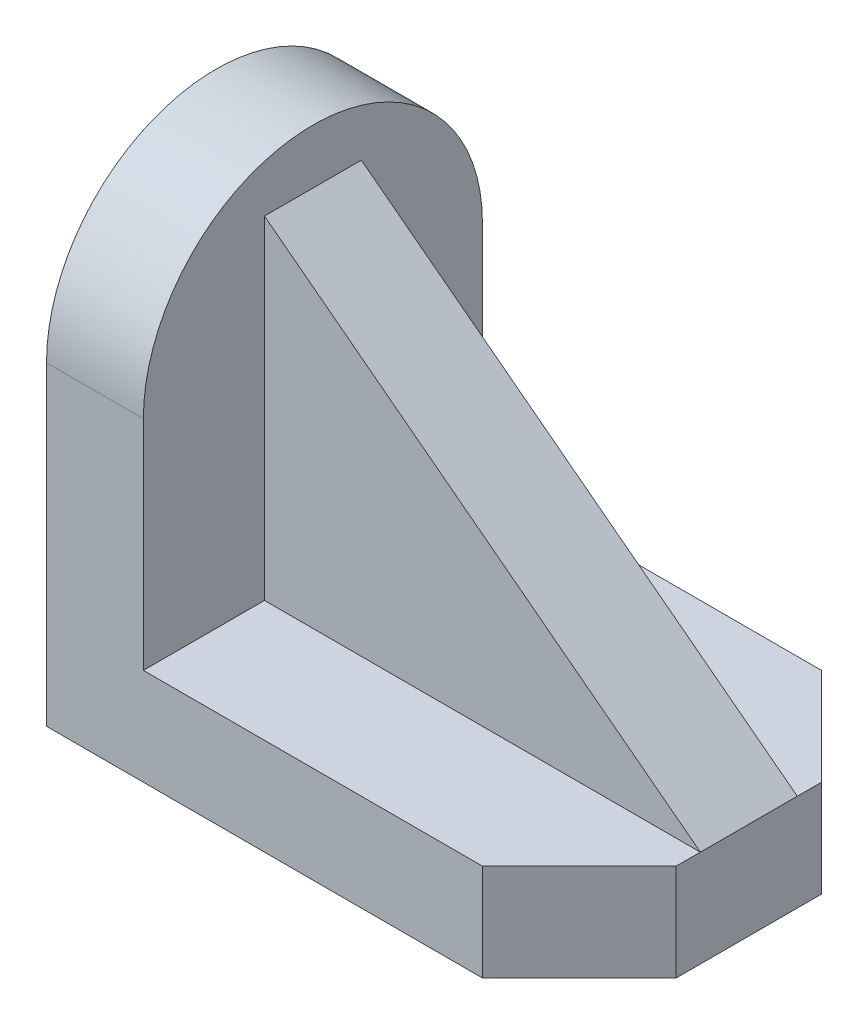
SolidWorks part; units mm, degrees
ref_plane "Front Plane" through (0, 0, 0) normal (0, 0, 1) x (1, 0, 0)
ref_plane "Top Plane" through (0, 0, 0) normal (0, 1, 0) x (1, 0, 0)
ref_plane "Right Plane" through (0, 0, 0) normal (1, 0, 0) x (0, 0, -1)
sketch "Sketch1" plane through (0, 0, 0) normal (0, 1, 0) x (1, 0, 0)
  line L1 (33, 21) -> (-33, 21)
  line L2 (33, 21) -> (33, -21)
  line L3 (33, -21) -> (-33, -21)
  line L4 (-33, 21) -> (-33, -21)
  line L5 (33, 21) -> (-33, -21) construction
  line L6 (33, -21) -> (-33, 21) construction
  point P0 (0, 0)
  dimension "D1" = 66
  dimension "D2" = 42
extrude "Boss-Extrude1" add sketch "Sketch1" along normal blind 12
fillet "Chamfer1" radius 12 1 edges at (33, 6, 21) profile chamfer
fillet "Chamfer2" radius 12 1 edges at (33, 6, -21) profile chamfer
sketch "Sketch2" plane through (0, 12, 0) normal (0, 1, 0) x (1, 0, 0)
  line L0 (-21, -6) -> (33, -6)
  line L1 (-21, -6) -> (-21, 6)
  line L2 (33, -6) -> (33, 6)
  line L3 (-21, 6) -> (33, 6)
  line L4 (33, -9) -> (33, 9) construction
  line L5 (-33, -21) -> (21, -21) construction
  line L6 (21, 21) -> (-33, 21) construction
  line L7 (-33, 21) -> (-33, -21) construction
  line L9 (-33, 21) -> (-21, 21)
  line L10 (-33, 21) -> (-33, -21)
  line L11 (-33, -21) -> (-21, -21)
  line L12 (-21, 21) -> (-21, -21)
  line M9 (33, -9) -> (33, 9)
  dimension "D1" = 15
  dimension "D2" = 15
  dimension "D3" = 12
  dimension "D4" = 12
extrude "Boss-Extrude2" add sketch "Sketch2" along normal blind 42 contours L3 L1 L0 M9 region at (6, 12, 0)
chamfer "Chamfer3" distance 42 distance2 55 1 edges at (33, 54, 0) first distance on face at (33, 19.5, 0)
sketch "Sketch4" plane through (0, 12, 0) normal (0, 1, 0) x (1, 0, 0)
  line L0 (-33, -21) -> (21, -21) construction
  line L1 (-21, -21) -> (-33, -21)
  line L2 (-21, -21) -> (-21, 21)
  line L3 (-21, 21) -> (-33, 21)
  line L4 (-33, -21) -> (-33, 21)
  dimension "D1" = 12
extrude "Boss-Extrude3" add sketch "Sketch4" along normal blind 27
sketch "Sketch7" plane through (0, 39, 0) normal (0, 1, 0) x (1, 0, 0)
  line L0 (0, 0) -> (-33, 0) construction
  line L1 (-33, 21) -> (-33, -21) construction
  line L3 (-33, 21) -> (-21, 21)
  line L4 (-33, 21) -> (-33, 0)
  line L5 (-33, 0) -> (-21, 0)
  line L6 (-21, 21) -> (-21, 0)
  dimension "D1" = 12
revolve "Revolve1" add sketch "Sketch7" angle 181 about L0 reverse direction yes
